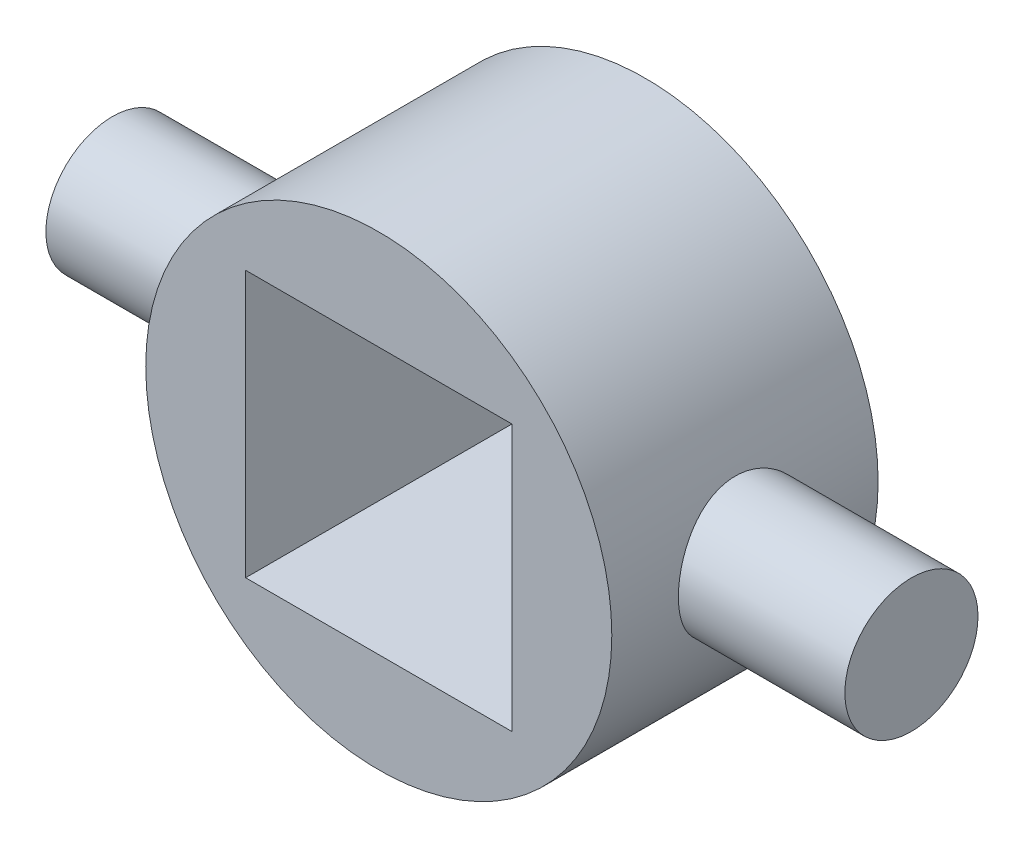
SolidWorks part; units mm, degrees
ref_plane "Спереди" through (0, 0, 0) normal (0, 0, 1) x (1, 0, 0)
ref_plane "Сверху" through (0, 0, 0) normal (0, 1, 0) x (1, 0, 0)
ref_plane "Справа" through (0, 0, 0) normal (1, 0, 0) x (0, 0, -1)
sketch "Эскиз1" plane through (0, 0, 0) normal (0, 0, 1) x (1, 0, 0)
  line L1 (-10, -10) -> (10, -10)
  line L2 (-10, -10) -> (-10, 10)
  line L3 (-10, 10) -> (10, 10)
  line L4 (10, -10) -> (10, 10)
  line L5 (-10, -10) -> (10, 10) construction
  line L6 (-10, 10) -> (10, -10) construction
  circle A0 centre (0, 0) radius 17.5
  dimension "D1" = 35
  dimension "D2" = 20
  dimension "D3" = 20
extrude "Бобышка-Вытянуть1" add sketch "Эскиз1" along normal blind 20
ref_plane "Плоскость1" through (17.5, 0, 0) normal (1, 0, 0) x (0, 0, -1)
sketch "Эскиз3" plane through (17.5, 0, 0) normal (1, 0, 0) x (0, 0, -1)
  line L0 (-20, 0) -> (0, 0) construction
  line L1 (-20, 17.5) -> (-20, -17.5) construction
  line L2 (-10, 17.5) -> (-10, -17.5) construction
  line L3 (0, 17.5) -> (-20, 17.5) construction
  line L4 (-20, -17.5) -> (0, -17.5) construction
  circle A0 centre (-10, 0) radius 5
  dimension "D1" = 10
extrude "Бобышка-Вытянуть2" add sketch "Эскиз3" along normal blind 12.5 and the other way up to surface other way up to face at (17.5, 0, 20)
ref_plane "Плоскость2" through (0, 0, 0) normal (-1, 0, 0) x (0, 0, 1)
mirror "Зеркальное отражение1" about plane through (0, 0, 0) normal (-1, 0, 0) of "Бобышка-Вытянуть2"
